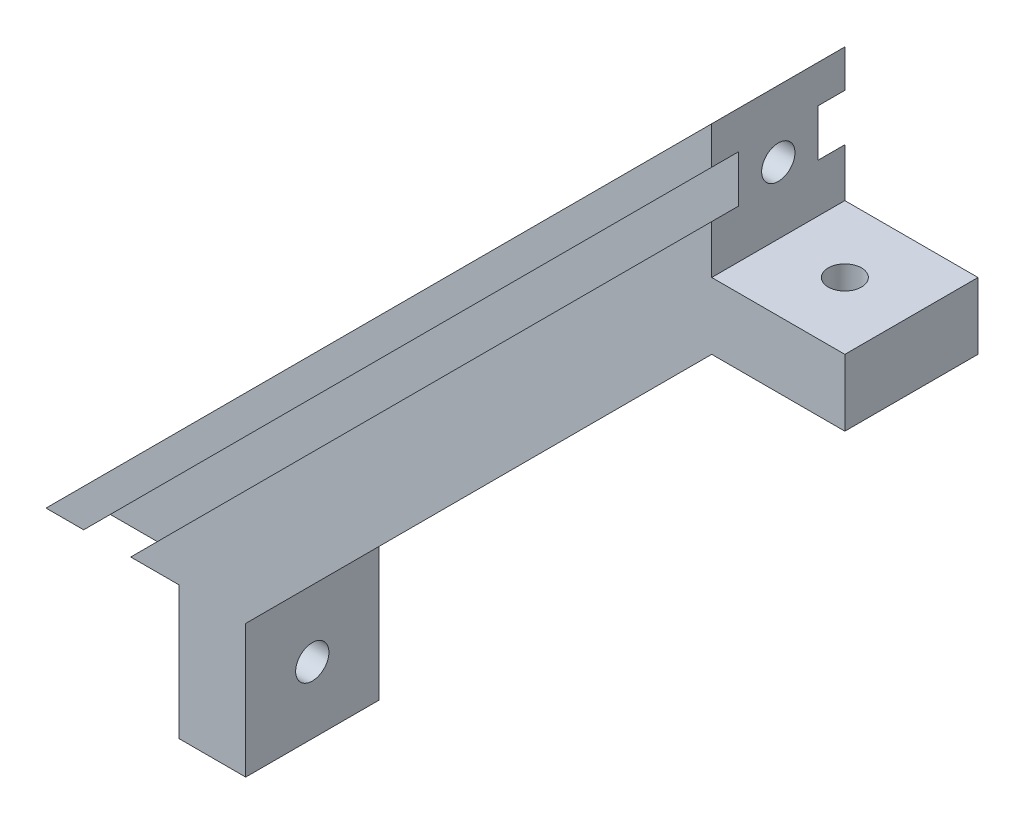
SolidWorks part; units mm, degrees
ref_plane "Front Plane" through (0, 0, 0) normal (0, 0, 1) x (1, 0, 0)
ref_plane "Top Plane" through (0, 0, 0) normal (0, 1, 0) x (1, 0, 0)
ref_plane "Right Plane" through (0, 0, 0) normal (1, 0, 0) x (0, 0, -1)
sketch "Sketch1" plane through (0, 0, 0) normal (0, 0, 1) x (1, 0, 0)
  line L0 (-25, -25) -> (25, 25)
  line L1 (25, 25) -> (25, 15)
  line L2 (-15, -25) -> (-15, -35)
  line L3 (-15, -35) -> (-10, -35)
  line L4 (25, 15) -> (35, 15)
  line L5 (-10, -35) -> (-10, -25)
  line L6 (-25, -25) -> (-15, -25)
  line L7 (-10, -25) -> (25, 10)
  line L8 (25, 10) -> (35, 10)
  line L9 (35, 15) -> (35, 10)
  point P4 (7.5, -7.5)
  point P11 (0, 0)
  point P13 (0, 0)
  dimension "D1" = 45
  dimension "D2" = 10
  dimension "D3" = 5
  dimension "D4" = 40
  dimension "D5" = 70.7107
extrude "Main" add sketch "Sketch1" along normal mid plane 10
sketch "Sketch2" plane through (25, 0, 0) normal (1, 0, 0) x (0, 0, -1)
  line L0 (5, -25) -> (-5, -35) construction
  line L1 (-5, -25) -> (5, -35) construction
  line L2 (-5, 15) -> (5, 25) construction
  line L3 (-5, 25) -> (5, 15) construction
  circle A0 centre (0, -30) radius 1.25
  circle A1 centre (0, 20) radius 1.25
  point P20 (5, 0)
  dimension "D1" = 2.5
extrude "FixHole1" cut sketch "Sketch2" against normal through all
sketch "Sketch3" plane through (0, -25, 0) normal (0, -1, 0) x (-1, 0, 0)
  line L0 (25, 5) -> (15, -5) construction
  line L1 (25, -5) -> (15, 5) construction
  line L2 (15, -5) -> (15, 5) construction
  line L3 (15, 5) -> (10, 5) construction
  line L4 (-25, 5) -> (-35, -5) construction
  line L5 (-25, -5) -> (-35, 5) construction
  line L6 (25, -5) -> (25, 5) construction
  circle A0 centre (20, 0) radius 1.25
  circle A1 centre (-30, 0) radius 1.25
  point P23 (0, 5)
  dimension "D1" = 2.5
extrude "FixHole2" cut sketch "Sketch3" against normal through all
sketch "Sketch4" plane through (0, 0, 5) normal (0, 0, 1) x (1, 0, 0)
  line L0 (25, 22.1716) -> (-22.1716, -25)
  line L1 (-22.1716, -25) -> (-18.636, -25)
  line L2 (-18.636, -25) -> (25, 18.636)
  line L3 (25, 18.636) -> (25, 22.1716)
  line L4 (25, 25) -> (-25, -25) construction
  line L5 (-25, -25) -> (-15, -25) construction
  line L6 (25, 15) -> (25, 25) construction
  point P6 (59.9904, 57.3034)
  point P7 (63.6068, 57.1014)
  point P8 (2.7301, 0)
  point P11 (6.6948, 0.1894)
  point P12 (6.5009, 0)
  point P13 (53.026, 50.339)
  point P14 (60, 53.4943)
  point P17 (60, 57.3464)
  dimension "D1" = 2.5
  dimension "D2" = 2
  dimension "D3" = 66.7107
  dimension "D4" = 61.7107
extrude "WindowSlot1" cut sketch "Sketch4" against normal blind 2
mirror "Mirror1" about plane through (0, 0, 0) normal (0, 0, 1) of "WindowSlot1"
sketch "Sketch6" plane through (7.5, -7.5, 0) normal (-0.7071, 0.7071, 0) x (0, 0, 1)
  circle A0 centre (0, 20) radius 1.25
  point P2 (0, 0)
  point P4 (0.584, 27.9464)
  dimension "D1" = 2.5
  dimension "D2" = 20
extrude "Cut-Extrude2" cut sketch "Sketch6" along normal blind 3
pattern_linear "LPattern1" count 5 spacing 10 along (-0.7071, -0.7071, 0) of "Cut-Extrude2"
